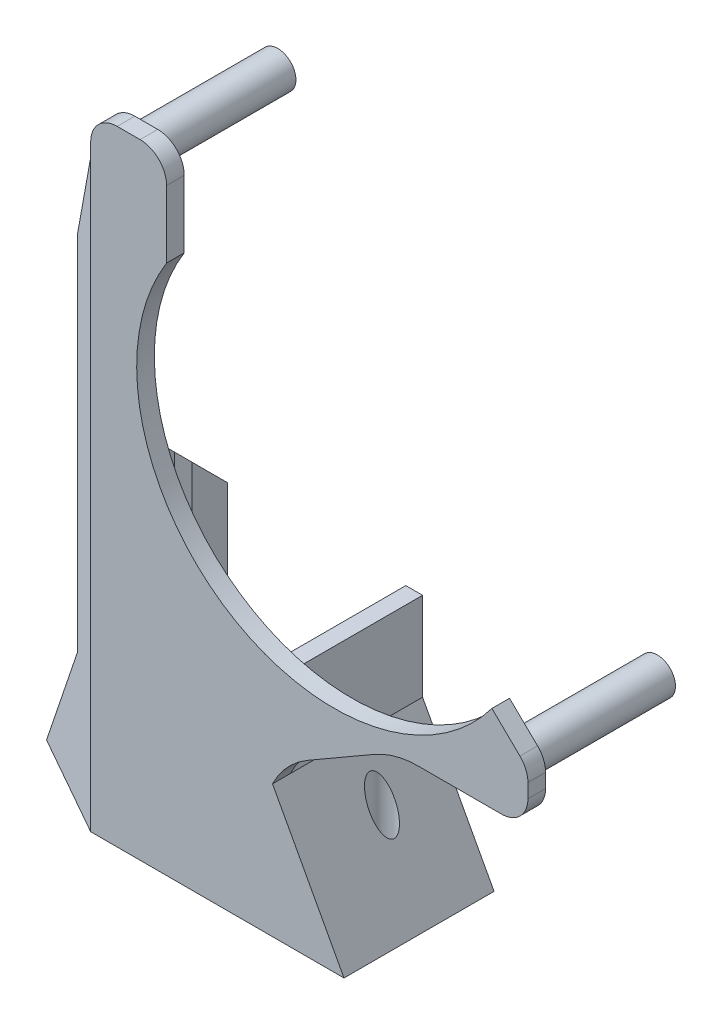
SolidWorks part; units mm, degrees
ref_plane "Front Plane" through (0, 0, 0) normal (0, 0, 1) x (1, 0, 0)
ref_plane "Top Plane" through (0, 0, 0) normal (0, 1, 0) x (1, 0, 0)
ref_plane "Right Plane" through (0, 0, 0) normal (1, 0, 0) x (0, 0, -1)
sketch "Sketch1" plane through (0, 0, 0) normal (0, 0, 1) x (1, 0, 0)
  line L1 (-12, -12.5) -> (12, -12.5)
  line L2 (-12, -12.5) -> (-12, 12.5)
  line L3 (-12, 12.5) -> (12, 12.5)
  line L4 (12, -12.5) -> (12, 12.5)
  line L5 (-12, -12.5) -> (12, 12.5) construction
  line L6 (-12, 12.5) -> (12, -12.5) construction
  point P0 (0, 0)
  dimension "D1" = 24
  dimension "D2" = 25
extrude "Boss-Extrude1" add sketch "Sketch1" along normal blind 17
sketch "Sketch2" plane through (0, 12.5, 0) normal (0, 1, 0) x (1, 0, 0)
  line L0 (-12, -8.5) -> (12, -8.5) construction
  line L1 (-12, -17) -> (-12, 0) construction
  line L2 (12, -17) -> (12, 0) construction
  line L3 (0, 0) -> (0, -17) construction
  line L4 (12, -17) -> (-12, -17) construction
  line L5 (12, 0) -> (-12, 0) construction
  line L10 (-10.1, 0) -> (10.1, 0)
  line L11 (-10.1, 0) -> (-10.1, -15)
  line L12 (-10.1, -15) -> (10.1, -15)
  line L13 (10.1, 0) -> (10.1, -15)
  point P11 (0, -8.5)
  point P18 (0, 0)
  dimension "D1" = 20.2
  dimension "D3" = 2
extrude "Cut-Extrude1" cut sketch "Sketch2" against normal through all
sketch "Sketch3" plane through (0, 0, 17) normal (0, 0, 1) x (1, 0, 0)
  line L0 (-12, -12.5) -> (-20.1, -12.5)
  line L1 (-20.1, -12.5) -> (-12, 2.5)
  line L2 (-12, 12.5) -> (-12, -12.5) construction
  line L3 (-12, 2.5) -> (-12, -12.5)
  line L4 (12, -12.5) -> (20.1, -12.5)
  line L5 (20.1, -12.5) -> (12, 2.5)
  line L6 (12, -12.5) -> (12, 12.5) construction
  line L7 (12, 2.5) -> (12, -12.5)
  dimension "D1" = 15
  dimension "D2" = 8.1
  dimension "D3" = 15
  dimension "D4" = 8.1
extrude "Boss-Extrude2" add sketch "Sketch3" against normal up to surface (17 mm away) up to face at (-11.05, 0, 0)
sketch "Sketch5" plane through (0, -12.5, 0) normal (0, -1, 0) x (1, 0, 0)
  line L4 (-20.1, 0) -> (-10.1, 0) construction
  circle A0 centre (-14.9, 7.5) radius 1.4
  circle A1 centre (14.9, 7.5) radius 1.4
  dimension "D1" = 2.8
  dimension "D2" = 7.5
  dimension "D3" = 14.9
  dimension "D4" = 14.9
extrude "Cut-Extrude5" cut sketch "Sketch5" against normal through all
sketch "Sketch6" plane through (0, 0, 17) normal (0, 0, 1) x (1, 0, 0)
  line L0 (12, 12.5) -> (40.9352, 12.5)
  line L7 (-12, 12.5) -> (-12, 43.5591)
  line L8 (-8.6, 58.2071) -> (0, 58.2071)
  line L9 (0, 58.2071) -> (0, 47.5958)
  line L13 (-20.1, -12.5) -> (20.1, -12.5)
  line L14 (-12, 12.5) -> (-12, 2.5)
  line L15 (12, 2.5) -> (12, 12.5)
  line L16 (12, 12.5) -> (-12, 12.5)
  line L17 (36.8559, 22.3265) -> (40.9352, 18.3575)
  line L18 (20.1, -12.5) -> (12, 2.5)
  line L22 (12, 12.5) -> (-12, 12.5)
  line L25 (40.9352, 18.3575) -> (40.9352, 12.5)
  line L26 (-8.6, 53.6676) -> (-12, 43.5591)
  line L28 (-8.6, 53.6676) -> (-8.6, 58.2071)
  line L30 (-12, 2.5) -> (-20.1, -12.5)
  arc A0 (1.812, 49.9809) -> (-3.5912, 35.4) centre (18.2849, 35.5849) ccw construction
  arc A1 (12.8512, 14.3286) -> (40.9, 34.9001) centre (19.3319, 34.9) ccw construction
  arc A2 (0, 47.5958) -> (36.8559, 22.3265) centre (18.9765, 35.7612) ccw
  dimension "D1" = 0
extrude "Boss-Extrude3" add sketch "Sketch6" against normal blind 2
sketch "Sketch4" plane through (0, 0, 0) normal (0, 1, 0) x (1, 0, 0)
  line L1 (12, -17) -> (-12, -17) construction
  line L27 (-8.6, -17) -> (-20.1, -17)
  line L32 (-20.1, -17) -> (-20.1, -10.5)
  line L33 (-20.1, 0) -> (-20.1, -17) construction
  line L34 (-20.1, -10.5) -> (-8.6, -17)
  dimension "D2" = 6.5
  dimension "D3" = 11.5
extrude "Cut-Extrude4" cut sketch "Sketch4" against normal through all both and the other way through all
sketch "Sketch7" plane through (0, 0, 15) normal (0, 0, -1) x (-1, 0, 0)
  circle A0 centre (-37.6, 16.9) radius 2.05
  circle A1 centre (5.4, 54.9) radius 2.05
  dimension "D1" = 4.1
extrude "Boss-Extrude4" add sketch "Sketch7" along normal blind 16
chamfer "Chamfer1" distance 1 angle 45 2 edges at (14.9, -12.5, 6.1) (-14.9, -12.5, 6.1)
chamfer "Chamfer2" distance 8 angle 60 1 edges at (12, 12.5, 16) first distance on face at (12, 8.5, 9.8)
fillet "Fillet1" radius 10 2 edges at (12, 4.5, 16) (25.8564, 12.5, 16)
sketch "Sketch8" plane through (0, 0, 15) normal (0, 0, -1) x (-1, 0, 0)
  line L0 (12, 43.5591) -> (12, 12.5) construction
  line L1 (10.1, 12.5) -> (12, 12.5)
  line L2 (10.1, 12.5) -> (10.1, 37.5)
  line L3 (10.1, 37.5) -> (12, 37.5)
  line L4 (12, 12.5) -> (12, 37.5)
  dimension "D1" = 25
extrude "Boss-Extrude5" add sketch "Sketch8" along normal blind 5
chamfer "Chamfer5" distance 5 angle 45 1 edges at (-11.05, 37.5, 15)
chamfer "Chamfer6" distance 10 angle 45 1 edges at (-11.05, 12.5, 10)
fillet "Fillet5" radius 3 4 edges at (40.9352, 18.3575, 16) (-8.6, 58.2071, 16) (0, 58.2071, 16) (40.9352, 12.5, 16)
sketch "Sketch9" plane through (-10.1, 0, 0) normal (1, 0, 0) x (0, 0, -1)
  line L0 (-7.5, -12.5) -> (-7.5, 14.514) construction
  line L1 (0, -12.5) -> (-15, -12.5) construction
  line L4 (-10, 4.3575) -> (-5, 4.3575)
  line L5 (-10, 4.3575) -> (-10, 24.6704)
  line L6 (-10, 24.6704) -> (-5, 24.6704)
  line L7 (-5, 4.3575) -> (-5, 24.6704)
  line L8 (-10, 4.3575) -> (-5, 24.6704) construction
  line L9 (-10, 24.6704) -> (-5, 4.3575) construction
  dimension "D1" = 5
extrude "Cut-Extrude6" cut sketch "Sketch9" against normal blind 1
chamfer "Chamfer7" distance 1 angle 45 3 edges at (-10.1, 10.9288, 5) (-10.1, 4.3575, 7.5) (-10.1, 20.9288, 10)
mirror "Mirror1" [suppressed] about plane through (0, 0, 0) normal (0, 0, 1) of bodies 121 114
delete or keep bodies "Body-Delete/Keep 1" [suppressed] type delete bodies bodies 121
